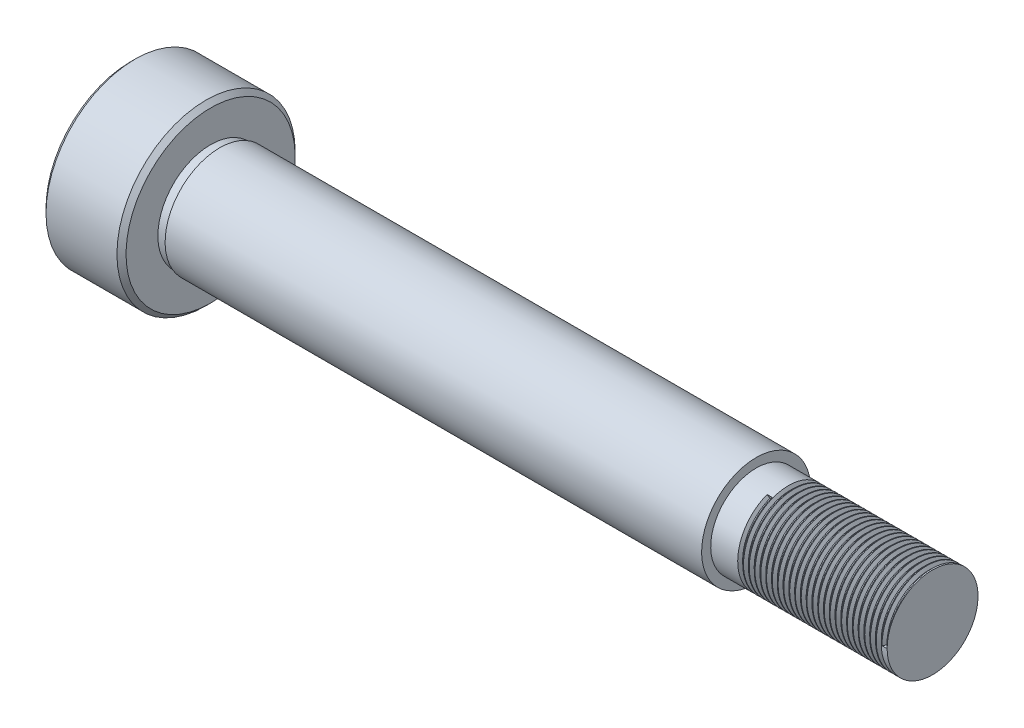
SolidWorks part; units mm, degrees
material "镀铬不锈钢"
ref_plane "前视基准面" through (0, 0, 0) normal (0, 0, 1) x (1, 0, 0)
ref_plane "上视基准面" through (0, 0, 0) normal (0, 1, 0) x (1, 0, 0)
ref_plane "右视基准面" through (0, 0, 0) normal (1, 0, 0) x (0, 0, -1)
sketch "Sketch1" plane through (0, 0, 0) normal (0, 0, 1) x (1, 0, 0)
  line L0 (0, 0) -> (0, 4.9)
  line L1 (0, 4.9) -> (4.4, 4.9)
  line L2 (4.4, 4.9) -> (4.4, 3)
  line L3 (4.4, 3) -> (34.4, 3)
  line L4 (34.4, 3) -> (34.4, 2.5)
  line L5 (34.4, 2.5) -> (44.1, 2.5)
  line L6 (44.1, 2.5) -> (44.1, 0)
  line L7 (44.1, 0) -> (0, 0)
  line L9 (4.4, 3) -> (4.9, 3)
  line L10 (4.4, 3) -> (4.4, 2.9)
  line L11 (4.4, 2.9) -> (4.9, 2.9)
  line L12 (4.9, 3) -> (4.9, 2.9)
  dimension "D1" = 4.9
  dimension "D2" = 3
  dimension "D3" = 2.5
  dimension "D4" = 4.4
  dimension "D5" = 9.7
  dimension "D6" = 30
  dimension "D7" = 0.1
  dimension "D8" = 0.5
revolve "Revolve1" add sketch "Sketch1" angle 360 about L7 region at (20.2196, 1.6057, 0)
sketch "Sketch2" plane through (0, 0, 0) normal (-1, 0, 0) x (0, 0, 1)
  line L1 (0, 1.7321) -> (-1.5, 0.866)
  line L2 (-1.5, 0.866) -> (-1.5, -0.866)
  line L3 (-1.5, -0.866) -> (0, -1.7321)
  line L4 (0, -1.7321) -> (1.5, -0.866)
  line L5 (1.5, -0.866) -> (1.5, 0.866)
  line L6 (1.5, 0.866) -> (0, 1.7321)
  circle A0 centre (0, 0) radius 1.5 construction
  dimension "D1" = 3
extrude "Extrude1" cut sketch "Sketch2" against normal blind 4
thread "螺纹线1" pitch 0.3175 method cut profile "Sketch4" start angle 0, offset 0, length 8, pitch 0.3175, diameter 5
ref_plane "Plane1" through (44.1, 0, 2.5) normal (0, -1, 0) x (0, 0, 1)
sketch "Sketch4" plane through (44.1, 0, 2.5) normal (0, -1, 0) x (0, 0, 1)
  line L0 (0, 0) -> (0, 0.3175) construction
  line L11 (0, 0) -> (0, 0.2778)
  line L12 (0, 0.2778) -> (-0.1719, 0.1786)
  line L13 (-0.1719, 0.1786) -> (-0.1719, 0.0992)
  line L15 (-0.1719, 0.0992) -> (0, 0)
  line L17 (-0.1719, 0.1389) -> (0, 0.1389) construction
  point P2 (0, 0)
  dimension "Pitch" = 0.3175
  dimension "Profile_Angle" = 60
  dimension "Profile_Land" = 0.0794
  dimension "Profile_Height" = 0.1719
chamfer "Chamfer2" distance 0.25 angle 45 2 edges at (0, 4.9, 0) (4.4, 4.9, 0)
